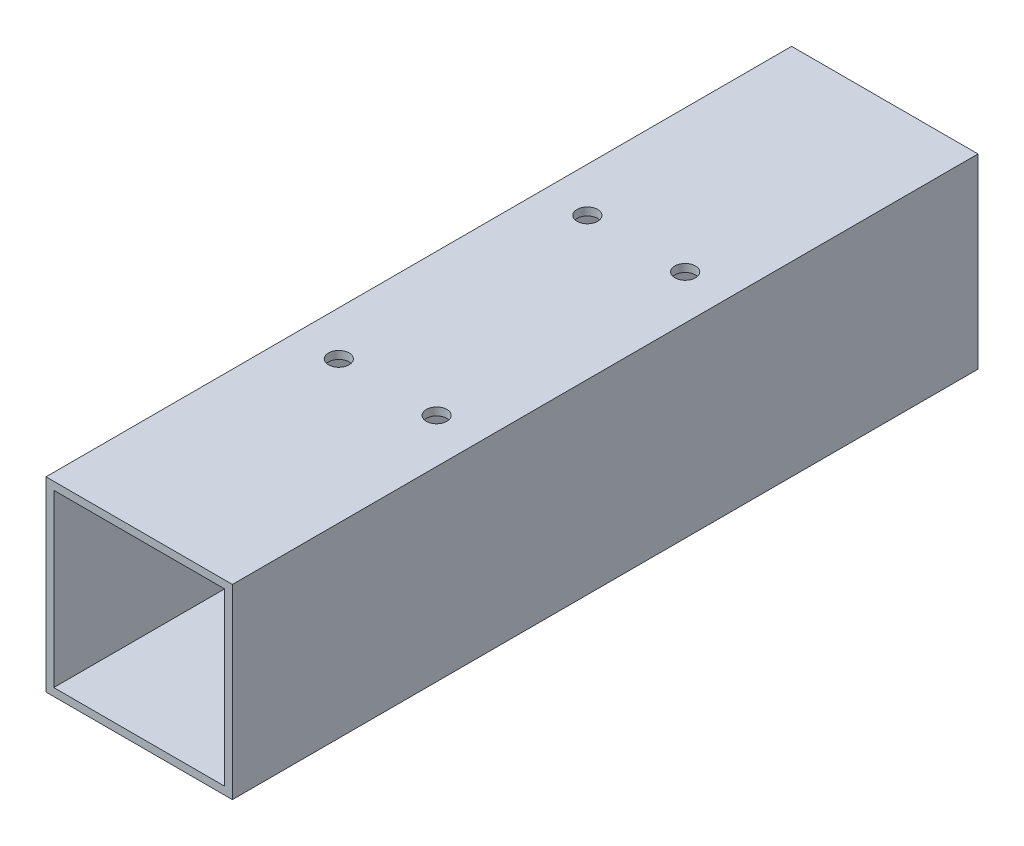
SolidWorks part; units mm, degrees
ref_plane "Front Plane" through (0, 0, 0) normal (0, 0, 1) x (1, 0, 0)
ref_plane "Top Plane" through (0, 0, 0) normal (0, 1, 0) x (1, 0, 0)
ref_plane "Right Plane" through (0, 0, 0) normal (1, 0, 0) x (0, 0, -1)
sketch "Sketch1" plane through (0, 0, 0) normal (0, 0, 1) x (1, 0, 0)
  line L0 (-34.925, 34.925) -> (34.925, 34.925)
  line L2 (-38.1, 38.1) -> (38.1, 38.1)
  line L3 (-38.1, 38.1) -> (-38.1, -38.1)
  line L4 (-38.1, -38.1) -> (38.1, -38.1)
  line L5 (38.1, 38.1) -> (38.1, -38.1)
  line L10 (34.925, 34.925) -> (34.925, -34.925)
  line L11 (-34.925, -34.925) -> (34.925, -34.925)
  line L12 (-34.925, 34.925) -> (-34.925, -34.925)
  point P12 (0, 38.1)
  point P14 (38.1, 0)
  dimension "Wall Thickness" = 3.175
  dimension "Outside Width" = 76.2
  dimension "Outside Height" = 76.2
  dimension "Inside Height" = 69.85
  dimension "Inside Width" = 69.85
sketch "Sketch2" plane through (0, 0, 0) normal (1, 0, 0) x (0, 0, -1)
  line L0 (152.4, 0) -> (-152.4, 0)
  point P4 (0, 0)
  point P7 (-152.4, 0)
  point P10 (152.4, 0)
  dimension "Length" = 304.8
sketch "Sketch3" plane through (0, 0, 0) normal (0, 0, 1) x (1, 0, 0)
  line L21 (38.1, 38.1) -> (-38.1, 38.1)
  line L22 (38.1, -38.1) -> (38.1, 38.1)
  line L23 (-38.1, -38.1) -> (38.1, -38.1)
  line L24 (-38.1, 38.1) -> (-38.1, -38.1)
  line L25 (38.1, 38.1) -> (-38.1, 38.1)
  line L26 (38.1, -38.1) -> (38.1, 38.1)
  line L27 (-38.1, -38.1) -> (38.1, -38.1)
  line L28 (-38.1, 38.1) -> (-38.1, -38.1)
  line L29 (34.925, 34.925) -> (-34.925, 34.925)
  line L30 (34.925, -34.925) -> (34.925, 34.925)
  line L31 (-34.925, -34.925) -> (34.925, -34.925)
  line L32 (-34.925, 34.925) -> (-34.925, -34.925)
  line L33 (34.925, 34.925) -> (-34.925, 34.925)
  line L34 (34.925, -34.925) -> (34.925, 34.925)
  line L35 (-34.925, -34.925) -> (34.925, -34.925)
  line L36 (-34.925, 34.925) -> (-34.925, -34.925)
  dimension "D1" = 0
  dimension "D2" = 0
extrude "Boss-Extrude1" add sketch "Sketch3" along normal up to vertex (152.4 mm away) and the other way up to vertex (152.4 mm away) up to point (0, 0, 152.4) other way up to point (0, 0, -152.4)
sketch "Drawing Reference" plane through (0, 0, 0) normal (1, 0, 0) x (0, 0, -1)
  line L0 (-152.4, 0) -> (152.4, 0) construction
  line L1 (0, -38.1) -> (0, 38.1) construction
  line L2 (-152.4, -38.1) -> (152.4, -38.1) construction
  line L5 (-152.4, 38.1) -> (152.4, 38.1) construction
  point P7 (-129.54, 0)
  point P8 (129.54, 0)
  dimension "D1" = 22.86
hole_wizard "5/16 Clearance Hole3" positions "Sketch12" profile "Sketch13" hole size "5/16" standard "ANSI Inch" end condition through all
sketch "Sketch12" plane through (0, -38.1, 0) normal (0, -1, 0) x (-1, 0, 0)
  line L1 (-20, -50.8) -> (20, -50.8)
  line L2 (-20, -50.8) -> (-20, 50.8)
  line L3 (-20, 50.8) -> (20, 50.8)
  line L4 (20, -50.8) -> (20, 50.8)
  line L5 (-20, -50.8) -> (20, 50.8) construction
  line L6 (-20, 50.8) -> (20, -50.8) construction
  point P2 (20, 50.8)
  point P127 (-20, -50.8)
  point P128 (-20, 50.8)
  point P129 (20, -50.8)
  point P143 (0, 0)
  dimension "D1" = 101.6
  dimension "D2" = 40
sketch "Sketch13" plane through (-20, -38.1, -50.8) normal (1, 0, 0) x (0, 0, -1)
  line L0 (0, 0) -> (0, 76.2)
  line L1 (0, 76.2) -> (4.2164, 76.2)
  line L2 (4.2164, 76.2) -> (4.2164, 0)
  line L5 (4.2164, 0) -> (0, 0)
  line L11 (0, -6.35) -> (0, 107.95) construction
  dimension "Thru Hole Dia." = 8.4328
  dimension "Thru Hole Depth" = 76.2
hole_wizard "1/2 Clearance Hole1" positions "Sketch14" profile "Sketch15" hole size "1/2" standard "ANSI Inch"
sketch "Sketch14" plane through (0, -38.1, 0) normal (0, -1, 0) x (-1, 0, 0)
  point P0 (-20, 50.8)
  point P3 (20, 50.8)
  point P6 (-20, -50.8)
  point P9 (20, -50.8)
sketch "Sketch15" plane through (20, -38.1, -50.8) normal (1, 0, 0) x (0, 0, -1)
  line L0 (0, 0) -> (0, 7.2285)
  line L1 (0, 7.2285) -> (6.7462, 3.175)
  line L2 (6.7462, 3.175) -> (6.7462, 0)
  line L5 (6.7462, 0) -> (0, 0)
  line L10 (0, 7.2285) -> (-6.7462, 3.175) construction
  line L11 (0, -6.35) -> (0, 107.95) construction
  dimension "Hole Dia." = 13.4925
  dimension "Hole Depth" = 3.175
  dimension "Drill Angle" = 118
sketch "Sketch16" plane through (0, -38.1, 0) normal (0, -1, 0) x (1, 0, 0)
  line L0 (0, -152.4) -> (0, 152.4) construction
  line L1 (-38.1, -152.4) -> (38.1, -152.4) construction
  line L2 (-38.1, 152.4) -> (38.1, 152.4) construction
  line L4 (38.1, 152.4) -> (38.1, -152.4) construction
  line L5 (38.1, 0) -> (-38.1, 0) construction
  line L6 (-38.1, 152.4) -> (-38.1, -152.4) construction
  point P12 (0, 0)
equation "\"D1@Drawing Reference\"=\"Outside Width@Sketch1\" * .3"
